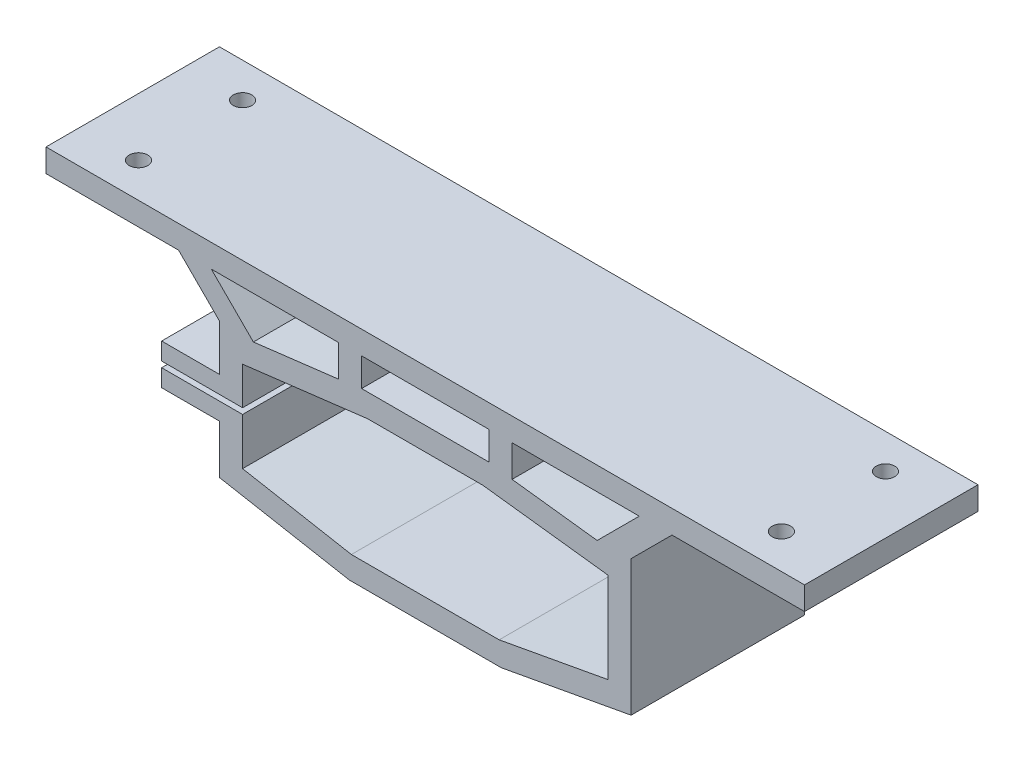
SolidWorks part; units mm, degrees
ref_plane "Front Plane" through (0, 0, 0) normal (0, 0, 1) x (1, 0, 0)
ref_plane "Top Plane" through (0, 0, 0) normal (0, 1, 0) x (1, 0, 0)
ref_plane "Right Plane" through (0, 0, 0) normal (1, 0, 0) x (0, 0, -1)
ref_plane "Plane1" through (0, 0, 70) normal (0, 0, 1) x (1, 0, 0)
sketch "Sketch2" plane through (0, 0, 70) normal (0, 0, 1) x (1, 0, 0)
  line L0 (31.6, 1.9592) -> (31.6, -13.6905)
  line L1 (31.6, -13.6905) -> (12.7818, -17.1405)
  line L2 (12.7818, -17.1405) -> (-12.7818, -17.1405)
  line L3 (-12.7818, -17.1405) -> (-31.6, -13.6905)
  line L4 (-31.6, -13.6905) -> (-31.6, -5.5711)
  line L5 (-31.6, 1.9592) -> (-9.9453, 4.6)
  line L6 (-9.9453, 4.6) -> (9.9453, 4.6)
  line L7 (9.9453, 4.6) -> (31.6, 1.9592)
  line L8 (22.4, 2.9804) -> (23.5, 2.8462) construction
  line L9 (-23.5, 2.8462) -> (-22.4, 2.9804) construction
  line L10 (-12.9528, -17.0075) -> (-29.7865, -13.9213) construction
  line L11 (29.7865, -13.9213) -> (12.9528, -17.0075) construction
  line L12 (-31.6, -4.5711) -> (-45.6, -4.5711)
  line L13 (12.6662, -17.0405) -> (-12.6662, -17.0405) construction
  line L14 (-7, 4.5) -> (-5.9, 4.5) construction
  line L15 (35.6, 6.4289) -> (35.6, -17.0239)
  line L16 (35.6, -17.0239) -> (13.1455, -21.1405)
  line L17 (13.1455, -21.1405) -> (-13.1455, -21.1405)
  line L18 (-13.1455, -21.1405) -> (-35.6, -17.0239)
  line L19 (-35.6, -17.0239) -> (-35.6, -8.5711)
  line L20 (-35.6, -8.5711) -> (-45.6, -8.5711)
  line L21 (-45.6, -8.5711) -> (-45.6, -5.5711)
  line L22 (-45.6, -1.5711) -> (-35.6, -1.5711)
  line L23 (-35.6, -1.5711) -> (-35.6, 6.4289)
  line L24 (-35.6, 6.4289) -> (-42.6711, 13.5)
  line L25 (-42.6711, 13.5) -> (-65.6, 13.5)
  line L26 (-65.6, 13.5) -> (-65.6, 17.5)
  line L27 (-90, 17.5) -> (-26.639, 17.5) construction
  line L28 (-65.6, 17.5) -> (65.6, 17.5)
  line L29 (26.639, 17.5) -> (90, 17.5) construction
  line L30 (65.6, 17.5) -> (65.6, 13.5)
  line L31 (65.6, 13.5) -> (42.6711, 13.5)
  line L32 (42.6711, 13.5) -> (35.6, 6.4289)
  line L33 (37.0142, 13.5) -> (29.731, 6.2168)
  line L34 (29.731, 6.2168) -> (15.0142, 8.0115)
  line L35 (15.0142, 8.0115) -> (15.0142, 13.5)
  line L36 (15.0142, 13.5) -> (37.0142, 13.5)
  line L37 (11.0142, 13.5) -> (11.0142, 8.6)
  line L38 (11.0142, 8.6) -> (-11.0142, 8.6)
  line L39 (-11.0142, 8.6) -> (-11.0142, 13.5)
  line L40 (-11.0142, 13.5) -> (11.0142, 13.5)
  line L41 (-15.0142, 13.5) -> (-15.0142, 8.0115)
  line L42 (-15.0142, 8.0115) -> (-29.731, 6.2168)
  line L43 (-29.731, 6.2168) -> (-37.0142, 13.5)
  line L44 (-37.0142, 13.5) -> (-15.0142, 13.5)
  line L46 (-45.6, -5.5711) -> (-31.6, -5.5711)
  line L47 (-45.6, -4.5711) -> (-45.6, -1.5711)
  line L48 (-31.6, -4.5711) -> (-31.6, 1.9592)
  point P54 (0, 8.6)
  point P58 (33.3726, 9.8584)
  dimension "D1" = 0.1
  dimension "D2" = 0.1
  dimension "D3" = 0.1
  dimension "D4" = 0.1
  dimension "D5" = 0.1
  dimension "D6" = 0.1
  dimension "D7" = 0.1
  dimension "D8" = 0.1
  dimension "D9" = 135
  dimension "D10" = 135
  dimension "D11" = 4
  dimension "D12" = 4
  dimension "D13" = 4
  dimension "D14" = 4
  dimension "D15" = 4
  dimension "D16" = 4
  dimension "D17" = 4
  dimension "D18" = 4
  dimension "D19" = 4
  dimension "D20" = 4
  dimension "D21" = 4
  dimension "D22" = 4
  dimension "D23" = 4
  dimension "D24" = 4
  dimension "D25" = 30
  dimension "D26" = 30
  dimension "D27" = 10
  dimension "D28" = 10
  dimension "D29" = 22
  dimension "D30" = 1
  dimension "D31" = 3
  dimension "D32" = 3
  dimension "D33" = 10
  dimension "D34" = 8
extrude "Extrude1" add sketch "Sketch2" along normal blind 20 and the other way blind 10
sketch "Sketch3" plane through (0, 13.5, 0) normal (0, -1, 0) x (1, 0, 0)
  line L0 (-65.6, 60) -> (-65.6, 90) construction
  line L1 (-55.6, 84) -> (55.6, 84) construction
  line L2 (-55.6, 84) -> (-55.6, 66) construction
  line L3 (-55.6, 66) -> (55.6, 66) construction
  line L4 (55.6, 84) -> (55.6, 66) construction
  line L5 (65.6, 60) -> (65.6, 90) construction
  line L6 (42.6711, 90) -> (65.6, 90) construction
  line L7 (42.6711, 60) -> (65.6, 60) construction
  circle A0 centre (-55.6, 84) radius 1.6
  circle A1 centre (-55.6, 66) radius 1.6
  circle A2 centre (55.6, 84) radius 1.6
  circle A3 centre (55.6, 66) radius 1.6
  dimension "D5" = 3.2
  dimension "D1" = 10
  dimension "D2" = 10
  dimension "D3" = 6
  dimension "D4" = 6
extrude "Cut-Extrude1" cut sketch "Sketch3" against normal blind 20
sketch "Sketch4" plane through (0, -8.5711, 0) normal (0, -1, 0) x (1, 0, 0)
  line L0 (-45.6, 60) -> (-45.6, 90) construction
  circle A0 centre (-41.6, 75) radius 2.15
  point P4 (-45.6, 75)
  dimension "D1" = 4
  dimension "D2" = 4.3
extrude "Cut-Extrude2" cut sketch "Sketch4" against normal blind 15
